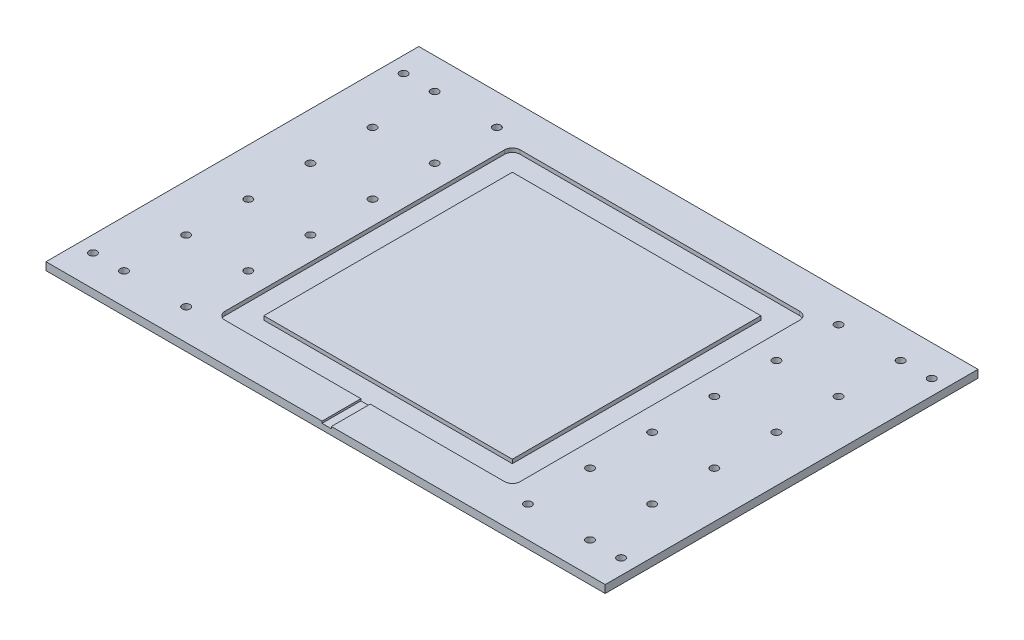
SolidWorks part; units mm, degrees
ref_plane "Front Plane" through (0, 0, 0) normal (0, 0, 1) x (1, 0, 0)
ref_plane "Top Plane" through (0, 0, 0) normal (0, 1, 0) x (1, 0, 0)
ref_plane "Right Plane" through (0, 0, 0) normal (1, 0, 0) x (0, 0, -1)
sketch "Sketch1" plane through (0, 0, 0) normal (0, 1, 0) x (1, 0, 0)
  line L1 (-0.2857, 0) -> (456.9143, 0)
  line L2 (-0.2857, 0) -> (-0.2857, 304.8)
  line L3 (-0.2857, 304.8) -> (456.9143, 304.8)
  line L4 (456.9143, 0) -> (456.9143, 304.8)
  circle A0 centre (38.1, 25.4) radius 3.175
  circle A1 centre (38.1, 76.2) radius 3.175
  circle A2 centre (38.1, 127) radius 3.175
  circle A3 centre (38.1, 228.6) radius 3.175
  circle A4 centre (38.1, 279.4) radius 3.175
  circle A5 centre (38.1, 177.8) radius 3.175
  circle A6 centre (88.9, 279.4) radius 3.175
  circle A7 centre (88.9, 228.6) radius 3.175
  circle A8 centre (88.9, 177.8) radius 3.175
  circle A9 centre (88.9, 127) radius 3.175
  circle A10 centre (88.9, 76.2) radius 3.175
  circle A11 centre (88.9, 25.4) radius 3.175
  circle A12 centre (368.3, 279.4) radius 3.175
  circle A13 centre (419.1, 228.6) radius 3.175
  circle A14 centre (419.1, 177.8) radius 3.175
  circle A15 centre (368.3, 127) radius 3.175
  circle A16 centre (368.3, 76.2) radius 3.175
  circle A17 centre (368.3, 25.4) radius 3.175
  circle A18 centre (419.1, 279.4) radius 3.175
  circle A19 centre (419.1, 127) radius 3.175
  circle A20 centre (419.1, 76.2) radius 3.175
  circle A21 centre (419.1, 25.4) radius 3.175
  circle A22 centre (368.3, 177.8) radius 3.175
  circle A23 centre (368.3, 228.6) radius 3.175
extrude "Boss-Extrude2" add sketch "Sketch1" along normal blind 6.35 contours L2 L1 L4 L3
extrude "Cut-Extrude3" cut sketch "Sketch1<5>" along normal blind 6.35 flip side to cut
sketch "Sketch1<5>" plane through (0, 0, 0) normal (0, 1, 0) x (1, 0, 0) same geometry as "Sketch1"
sketch "Sketch5" plane through (0, 6.35, 0) normal (0, 1, 0) x (1, 0, 0)
  line L3 (127, 254) -> (330.2, 254)
  line L4 (127, 254) -> (127, 50.8)
  line L5 (127, 50.8) -> (330.2, 50.8)
  line L6 (330.2, 254) -> (330.2, 50.8)
  line L14 (107.95, 273.05) -> (107.95, 31.75)
  line L15 (107.95, 31.75) -> (349.25, 31.75)
  line L16 (349.25, 273.05) -> (349.25, 31.75)
  line L17 (107.95, 273.05) -> (349.25, 273.05)
  dimension "D1" = 19.05
extrude "Cut-Extrude7" cut sketch "Sketch5" against normal blind 3.175
sketch "Sketch6" plane through (0, 6.35, 0) normal (0, 1, 0) x (1, 0, 0)
  line L0 (-0.2857, 0) -> (456.9143, 0) construction
  line L1 (225.425, 31.75) -> (233.045, 31.75)
  line L2 (225.425, 31.75) -> (225.425, 0)
  line L3 (225.425, 0) -> (233.045, 0)
  line L4 (233.045, 31.75) -> (233.045, 0)
  dimension "D1" = 7.62
extrude "Cut-Extrude8" cut sketch "Sketch6" against normal blind 1.5875
sketch "Sketch8" plane through (0, 6.35, 0) normal (0, 1, 0) x (1, 0, 0)
  line L2 (457.2, 0) -> (533.4, 0)
  line L3 (457.2, 0) -> (457.2, 304.8)
  line L4 (457.2, 304.8) -> (533.4, 304.8)
  line L5 (533.4, 0) -> (533.4, 304.8)
  circle A0 centre (520.7, 279.4) radius 3.175
  circle A1 centre (469.6659, 279.468) radius 3.175
  circle A2 centre (469.6659, 228.6) radius 3.175
  circle A3 centre (469.9, 177.8) radius 3.175
  circle A4 centre (469.9, 127) radius 3.175
  circle A5 centre (469.9, 76.2) radius 3.175
  circle A6 centre (469.9, 25.4) radius 3.175
  circle A7 centre (520.7, 228.6) radius 3.175
  circle A8 centre (520.7, 177.8) radius 3.175
  circle A9 centre (520.7, 127) radius 3.175
  circle A10 centre (520.7, 76.2) radius 3.175
  circle A11 centre (520.7, 25.4) radius 3.175
sketch "Sketch10" plane through (0, 0, 0) normal (0, 1, 0) x (1, 0, 0)
  line L0 (-76.2, 0) -> (0, 0)
  line L1 (-76.2, 0) -> (-76.2, 304.8)
  line L2 (-76.2, 304.8) -> (0, 304.8)
  line L3 (0, 0) -> (0, 304.8)
  circle A0 centre (-13.0225, 279.1203) radius 3.175
  circle A1 centre (-64.0566, 279.1883) radius 3.175
  circle A2 centre (-64.0566, 228.3203) radius 3.175
  circle A3 centre (-63.8225, 177.5203) radius 3.175
  circle A4 centre (-63.8225, 126.7203) radius 3.175
  circle A5 centre (-63.8225, 75.9203) radius 3.175
  circle A6 centre (-63.8225, 25.1203) radius 3.175
  circle A7 centre (-13.0225, 228.3203) radius 3.175
  circle A8 centre (-13.0225, 177.5203) radius 3.175
  circle A9 centre (-13.0225, 126.7203) radius 3.175
  circle A10 centre (-13.0225, 75.9203) radius 3.175
  circle A11 centre (-13.0225, 25.1203) radius 3.175
sketch "Sketch12" plane through (0, 0, 0) normal (0, -1, 0) x (1, 0, 0)
  circle A0 centre (12.7, -25.4) radius 3.175
  circle A1 centre (12.7, -279.4) radius 3.175
  circle A2 centre (444.5, -25.4) radius 3.175
  circle A3 centre (444.5, -279.4) radius 3.175
extrude "Cut-Extrude13" cut sketch "Sketch12" against normal blind 6.35
fillet "Fillet1" radius 6.35 4 edges at (349.25, 4.7625, -31.75) (107.95, 4.7625, -31.75) (349.25, 4.7625, -273.05) (107.95, 4.7625, -273.05)
